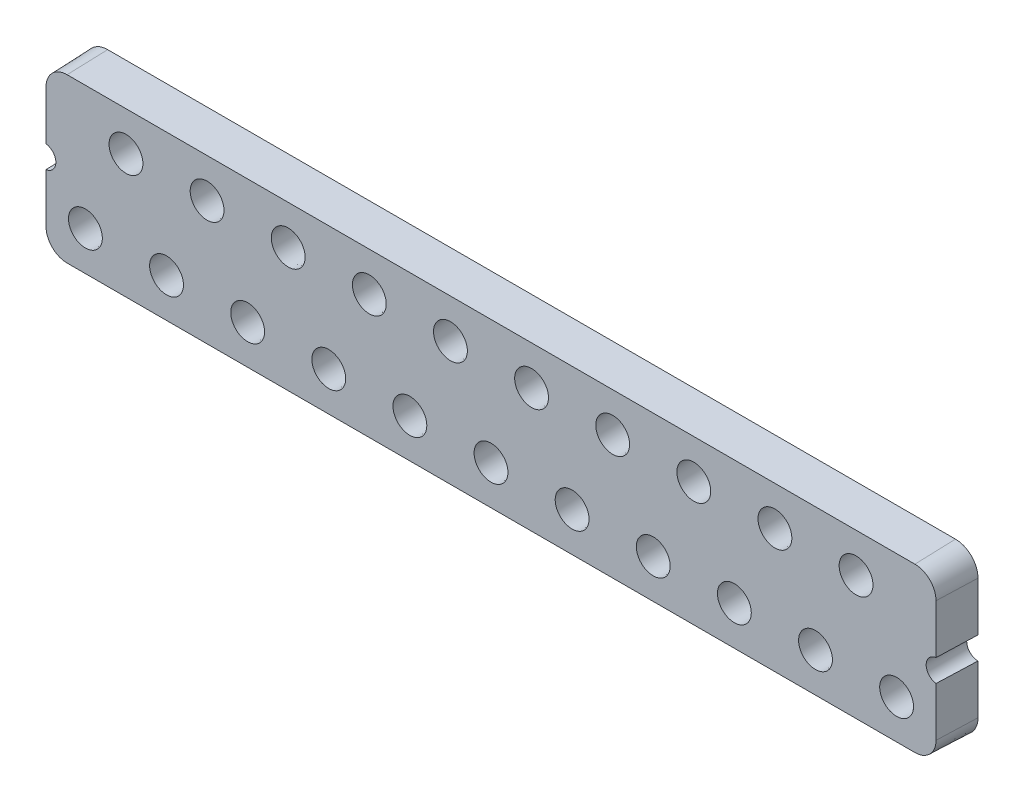
SolidWorks part; units mm, degrees
ref_plane "Front" through (0, 0, 0) normal (0, 0, 1) x (1, 0, 0)
ref_plane "Top" through (0, 0, 0) normal (0, 1, 0) x (1, 0, 0)
ref_plane "Right" through (0, 0, 0) normal (1, 0, 0) x (0, 0, -1)
sketch "Sketch11" plane through (0, 0, 0) normal (0, 0, 1) x (1, 0, 0)
  line L0 (19.812, 0.5) -> (19.812, -0.5)
  line L1 (18.812, 3.683) -> (-18.812, 3.683)
  line L2 (-19.812, 2.683) -> (-19.812, 0.5)
  line L3 (-19.812, -0.5) -> (-19.812, -2.683)
  line L4 (-18.812, -3.683) -> (18.812, -3.683)
  line L5 (19.812, -2.683) -> (19.812, -0.5)
  line L6 (19.812, 0.5) -> (19.812, 2.683)
  line L7 (-19.812, 0.5) -> (-19.812, -0.5)
  circle A0 centre (16.2, 1.885) radius 0.8 construction
  circle A1 centre (12.6, 1.885) radius 0.8 construction
  circle A2 centre (9, 1.885) radius 0.8 construction
  circle A3 centre (5.4, 1.885) radius 0.8 construction
  circle A4 centre (1.8, 1.885) radius 0.8 construction
  circle A5 centre (-1.8, 1.885) radius 0.8 construction
  circle A6 centre (-5.4, 1.885) radius 0.8 construction
  circle A7 centre (-9, 1.885) radius 0.8 construction
  circle A8 centre (-12.6, 1.885) radius 0.8 construction
  circle A9 centre (-16.2, 1.885) radius 0.8 construction
  circle A10 centre (-18, -1.885) radius 0.8 construction
  circle A11 centre (-14.4, -1.885) radius 0.8 construction
  circle A12 centre (-10.8, -1.885) radius 0.8 construction
  circle A13 centre (-7.2, -1.885) radius 0.8 construction
  circle A14 centre (-3.6, -1.885) radius 0.8 construction
  circle A15 centre (0, -1.885) radius 0.8 construction
  circle A16 centre (3.6, -1.885) radius 0.8 construction
  circle A17 centre (7.2, -1.885) radius 0.8 construction
  circle A18 centre (10.8, -1.885) radius 0.8 construction
  circle A19 centre (14.4, -1.885) radius 0.8 construction
  circle A20 centre (18, -1.885) radius 0.8 construction
  arc A21 (-19.812, 0.5) -> (-19.812, -0.5) centre (-19.812, 0) cw construction
  arc A22 (-18.812, 3.683) -> (-19.812, 2.683) centre (-18.812, 2.683) ccw
  arc A23 (-19.812, -2.683) -> (-18.812, -3.683) centre (-18.812, -2.683) ccw
  arc A24 (18.812, -3.683) -> (19.812, -2.683) centre (18.812, -2.683) ccw
  arc A25 (19.812, -0.5) -> (19.812, 0.5) centre (19.812, 0) cw construction
  arc A26 (19.812, 2.683) -> (18.812, 3.683) centre (18.812, 2.683) ccw
  circle A27 centre (16.2, 1.885) radius 1.205 construction
  circle A28 centre (12.6, 1.885) radius 1.205 construction
  circle A29 centre (9, 1.885) radius 1.205 construction
  circle A30 centre (5.4, 1.885) radius 1.205 construction
  circle A31 centre (1.8, 1.885) radius 1.205 construction
  circle A32 centre (-1.8, 1.885) radius 1.205 construction
  circle A33 centre (-5.4, 1.885) radius 1.205 construction
  circle A34 centre (-9, 1.885) radius 1.205 construction
  circle A35 centre (-12.6, 1.885) radius 1.205 construction
  circle A36 centre (-16.2, 1.885) radius 1.205 construction
  circle A37 centre (-18, -1.885) radius 1.205 construction
  circle A38 centre (-14.4, -1.885) radius 1.205 construction
  circle A39 centre (-10.8, -1.885) radius 1.205 construction
  circle A40 centre (-7.2, -1.885) radius 1.205 construction
  circle A41 centre (-3.6, -1.885) radius 1.205 construction
  circle A42 centre (0, -1.885) radius 1.205 construction
  circle A43 centre (3.6, -1.885) radius 1.205 construction
  circle A44 centre (7.2, -1.885) radius 1.205 construction
  circle A45 centre (10.8, -1.885) radius 1.205 construction
  circle A46 centre (14.4, -1.885) radius 1.205 construction
  circle A47 centre (18, -1.885) radius 1.205 construction
extrude "Boss-Extrude1" add sketch "Sketch11" along normal blind 1.8 draft 2
sketch "Sketch10" plane through (0, 0, 0) normal (0, 0, 1) x (1, 0, 0)
  line L1 (18.812, 3.683) -> (-18.812, 3.683) construction
  line L2 (-19.812, 2.683) -> (-19.812, 0.5) construction
  line L3 (-19.812, -0.5) -> (-19.812, -2.683) construction
  line L4 (-18.812, -3.683) -> (18.812, -3.683) construction
  line L5 (19.812, -2.683) -> (19.812, -0.5) construction
  line L6 (19.812, 0.5) -> (19.812, 2.683) construction
  circle A0 centre (16.2, 1.885) radius 0.805 construction
  circle A1 centre (12.6, 1.885) radius 0.805 construction
  circle A2 centre (9, 1.885) radius 0.805 construction
  circle A3 centre (5.4, 1.885) radius 0.805 construction
  circle A4 centre (1.8, 1.885) radius 0.805 construction
  circle A5 centre (-1.8, 1.885) radius 0.805 construction
  circle A6 centre (-5.4, 1.885) radius 0.805 construction
  circle A7 centre (-9, 1.885) radius 0.805 construction
  circle A8 centre (-12.6, 1.885) radius 0.805 construction
  circle A9 centre (-16.2, 1.885) radius 0.805 construction
  circle A10 centre (-18, -1.885) radius 0.805 construction
  circle A11 centre (-14.4, -1.885) radius 0.805 construction
  circle A12 centre (-10.8, -1.885) radius 0.805 construction
  circle A13 centre (-7.2, -1.885) radius 0.805 construction
  circle A14 centre (-3.6, -1.885) radius 0.805 construction
  circle A15 centre (0, -1.885) radius 0.805 construction
  circle A16 centre (3.6, -1.885) radius 0.805 construction
  circle A17 centre (7.2, -1.885) radius 0.805 construction
  circle A18 centre (10.8, -1.885) radius 0.805 construction
  circle A19 centre (14.4, -1.885) radius 0.805 construction
  circle A20 centre (18, -1.885) radius 0.805 construction
  arc A21 (-19.812, 0.5) -> (-19.812, -0.5) centre (-19.812, 0) cw construction
  arc A22 (-18.812, 3.683) -> (-19.812, 2.683) centre (-18.812, 2.683) ccw construction
  arc A23 (-19.812, -2.683) -> (-18.812, -3.683) centre (-18.812, -2.683) ccw construction
  arc A24 (18.812, -3.683) -> (19.812, -2.683) centre (18.812, -2.683) ccw construction
  arc A25 (19.812, -0.5) -> (19.812, 0.5) centre (19.812, 0) cw construction
  arc A26 (19.812, 2.683) -> (18.812, 3.683) centre (18.812, 2.683) ccw construction
  circle A27 centre (16.2, 1.885) radius 1.223
  circle A28 centre (12.6, 1.885) radius 1.223
  circle A29 centre (9, 1.885) radius 1.223
  circle A30 centre (5.4, 1.885) radius 1.223
  circle A31 centre (1.8, 1.885) radius 1.223
  circle A32 centre (-1.8, 1.885) radius 1.223
  circle A33 centre (-5.4, 1.885) radius 1.223
  circle A34 centre (-9, 1.885) radius 1.223
  circle A35 centre (-12.6, 1.885) radius 1.223
  circle A36 centre (-16.2, 1.885) radius 1.223
  circle A37 centre (-18, -1.885) radius 1.223
  circle A38 centre (-14.4, -1.885) radius 1.223
  circle A39 centre (-10.8, -1.885) radius 1.223
  circle A40 centre (-7.2, -1.885) radius 1.223
  circle A41 centre (-3.6, -1.885) radius 1.223
  circle A42 centre (0, -1.885) radius 1.223
  circle A43 centre (3.6, -1.885) radius 1.223
  circle A44 centre (7.2, -1.885) radius 1.223
  circle A45 centre (10.8, -1.885) radius 1.223
  circle A46 centre (14.4, -1.885) radius 1.223
  circle A47 centre (18, -1.885) radius 1.223
extrude "Cut-Extrude2" cut sketch "Sketch10" along normal blind 0.25 draft 2
sketch "Sketch9" plane through (0, 0, 0.25) normal (0, 0, 1) x (1, 0, 0)
  line L1 (18.812, 3.683) -> (-18.812, 3.683) construction
  line L2 (-19.812, 2.683) -> (-19.812, 0.5) construction
  line L3 (-19.812, -0.5) -> (-19.812, -2.683) construction
  line L4 (-18.812, -3.683) -> (18.812, -3.683) construction
  line L5 (19.812, -2.683) -> (19.812, -0.5) construction
  line L6 (19.812, 0.5) -> (19.812, 2.683) construction
  circle A0 centre (16.2, 1.885) radius 0.805
  circle A1 centre (12.6, 1.885) radius 0.805
  circle A2 centre (9, 1.885) radius 0.805
  circle A3 centre (5.4, 1.885) radius 0.805
  circle A4 centre (1.8, 1.885) radius 0.805
  circle A5 centre (-1.8, 1.885) radius 0.805
  circle A6 centre (-5.4, 1.885) radius 0.805
  circle A7 centre (-9, 1.885) radius 0.805
  circle A8 centre (-12.6, 1.885) radius 0.805
  circle A9 centre (-16.2, 1.885) radius 0.805
  circle A10 centre (-18, -1.885) radius 0.805
  circle A11 centre (-14.4, -1.885) radius 0.805
  circle A12 centre (-10.8, -1.885) radius 0.805
  circle A13 centre (-7.2, -1.885) radius 0.805
  circle A14 centre (-3.6, -1.885) radius 0.805
  circle A15 centre (0, -1.885) radius 0.805
  circle A16 centre (3.6, -1.885) radius 0.805
  circle A17 centre (7.2, -1.885) radius 0.805
  circle A18 centre (10.8, -1.885) radius 0.805
  circle A19 centre (14.4, -1.885) radius 0.805
  circle A20 centre (18, -1.885) radius 0.805
  arc A21 (-19.812, 0.5) -> (-19.812, -0.5) centre (-19.812, 0) cw construction
  arc A22 (-18.812, 3.683) -> (-19.812, 2.683) centre (-18.812, 2.683) ccw construction
  arc A23 (-19.812, -2.683) -> (-18.812, -3.683) centre (-18.812, -2.683) ccw construction
  arc A24 (18.812, -3.683) -> (19.812, -2.683) centre (18.812, -2.683) ccw construction
  arc A25 (19.812, -0.5) -> (19.812, 0.5) centre (19.812, 0) cw construction
  arc A26 (19.812, 2.683) -> (18.812, 3.683) centre (18.812, 2.683) ccw construction
  circle A27 centre (16.2, 1.885) radius 1.205 construction
  circle A28 centre (12.6, 1.885) radius 1.205 construction
  circle A29 centre (9, 1.885) radius 1.205 construction
  circle A30 centre (5.4, 1.885) radius 1.205 construction
  circle A31 centre (1.8, 1.885) radius 1.205 construction
  circle A32 centre (-1.8, 1.885) radius 1.205 construction
  circle A33 centre (-5.4, 1.885) radius 1.205 construction
  circle A34 centre (-9, 1.885) radius 1.205 construction
  circle A35 centre (-12.6, 1.885) radius 1.205 construction
  circle A36 centre (-16.2, 1.885) radius 1.205 construction
  circle A37 centre (-18, -1.885) radius 1.205 construction
  circle A38 centre (-14.4, -1.885) radius 1.205 construction
  circle A39 centre (-10.8, -1.885) radius 1.205 construction
  circle A40 centre (-7.2, -1.885) radius 1.205 construction
  circle A41 centre (-3.6, -1.885) radius 1.205 construction
  circle A42 centre (0, -1.885) radius 1.205 construction
  circle A43 centre (3.6, -1.885) radius 1.205 construction
  circle A44 centre (7.2, -1.885) radius 1.205 construction
  circle A45 centre (10.8, -1.885) radius 1.205 construction
  circle A46 centre (14.4, -1.885) radius 1.205 construction
  circle A47 centre (18, -1.885) radius 1.205 construction
extrude "Cut-Extrude3" cut sketch "Sketch9" along normal through all draft 2
sketch "Sketch12" plane through (0, 0, 0) normal (0, 0, 1) x (1, 0, 0)
  line L1 (19.812, -2.683) -> (19.812, 2.683) construction
  line L2 (-19.812, 2.683) -> (-19.812, -2.683) construction
  circle A0 centre (19.812, 0) radius 0.5
  circle A1 centre (-19.812, 0) radius 0.5
extrude "Cut-Extrude4" cut sketch "Sketch12" along normal through all
